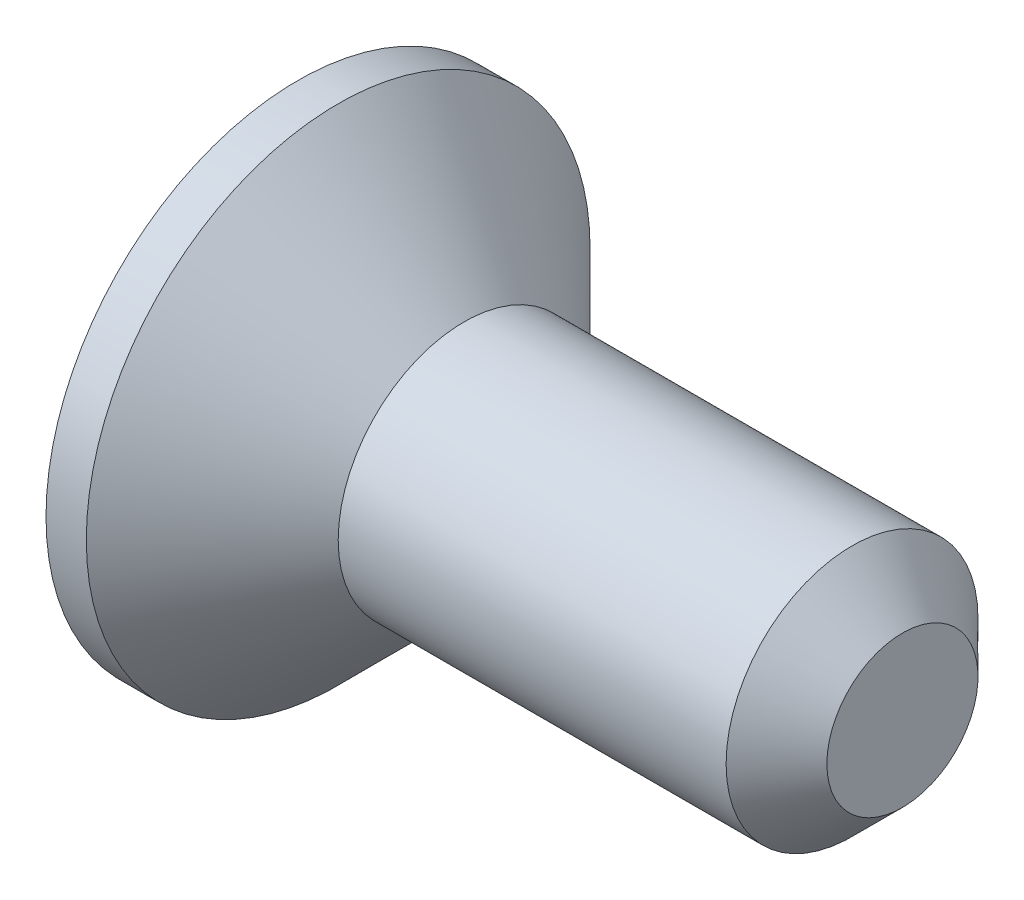
SolidWorks part; units mm, degrees
ref_plane "Front Plane" through (0, 0, 0) normal (0, 0, 1) x (1, 0, 0)
ref_plane "Top Plane" through (0, 0, 0) normal (0, 1, 0) x (1, 0, 0)
ref_plane "Right Plane" through (0, 0, 0) normal (1, 0, 0) x (0, 0, -1)
sketch "Sketch2" plane through (0, 0, 0) normal (0, 0, 1) x (1, 0, 0)
  line L0 (0, 0) -> (0, 2.5)
  line L1 (0, 2.5) -> (0.4, 2.5)
  line L2 (0.4, 2.5) -> (1.65, 1.25)
  line L3 (1.65, 1.25) -> (5.5, 1.25)
  line L4 (5.5, 1.25) -> (6, 0.75)
  line L5 (6, 0.75) -> (6, 0)
  line L6 (6, 0) -> (0, 0)
  line L7 (-2.2818, 0) -> (8.0811, 0) construction
  line L8 (1.65, 1.25) -> (0, 1.25) construction
  point P9 (5.2532, 1.25)
  dimension "D1" = 5
  dimension "D2" = 0.4
  dimension "D3" = 45
  dimension "D4" = 6
  dimension "D5" = 0.5
revolve "Revolve1" add sketch "Sketch2" angle 360 about L7
sketch "Sketch3" plane through (0, 0, 0) normal (-1, 0, 0) x (0, 0, 1)
  line L1 (0.433, -0.75) -> (0.866, 0)
  line L2 (0.866, 0) -> (0.433, 0.75)
  line L3 (0.433, 0.75) -> (-0.433, 0.75)
  line L4 (-0.433, 0.75) -> (-0.866, 0)
  line L5 (-0.866, 0) -> (-0.433, -0.75)
  line L6 (-0.433, -0.75) -> (0.433, -0.75)
  circle A0 centre (0, 0) radius 0.75 construction
  dimension "D1" = 1.5
extrude "Cut-Extrude1" cut sketch "Sketch3" against normal blind 0.8
